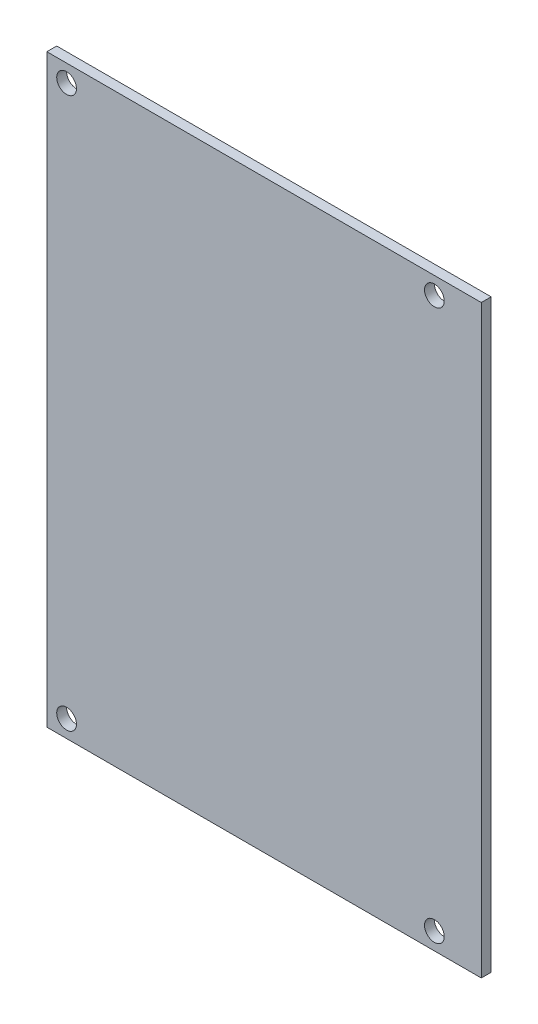
SolidWorks part; units mm, degrees
ref_plane "Plan de face" through (0, 0, 0) normal (0, 0, 1) x (1, 0, 0)
ref_plane "Plan de dessus" through (0, 0, 0) normal (0, 1, 0) x (1, 0, 0)
ref_plane "Plan de droite" through (0, 0, 0) normal (1, 0, 0) x (0, 0, -1)
sketch "Main-Sketch" plane through (0, 0, 0) normal (0, 0, 1) x (1, 0, 0)
  line L1 (0, 0) -> (88, 0)
  line L2 (0, 0) -> (0, 118.5)
  line L3 (0, 118.5) -> (88, 118.5)
  line L4 (88, 0) -> (88, 118.5)
  dimension "D1" = 88
  dimension "D2" = 118.5
extrude "Main-Extrusion" add sketch "Main-Sketch" along normal blind 2
sketch "Fix-Sketch" plane through (0, 0, 2) normal (0, 0, 1) x (1, 0, 0)
  line L0 (88, 118.5) -> (0, 118.5) construction
  line L2 (0, 118.5) -> (0, 0) construction
  line L3 (0, 0) -> (88, 0) construction
  circle A0 centre (4, 115) radius 2
  circle A1 centre (4, 3.5) radius 2
  circle A2 centre (78.5, 3.5) radius 2
  circle A3 centre (78.5, 115) radius 2
  dimension "D1" = 3.5
  dimension "D2" = 4
  dimension "D3" = 111.5
  dimension "D4" = 4
  dimension "D5" = 3.5
  dimension "D6" = 74.5
extrude "Fix-Hole" cut sketch "Fix-Sketch" against normal through all
